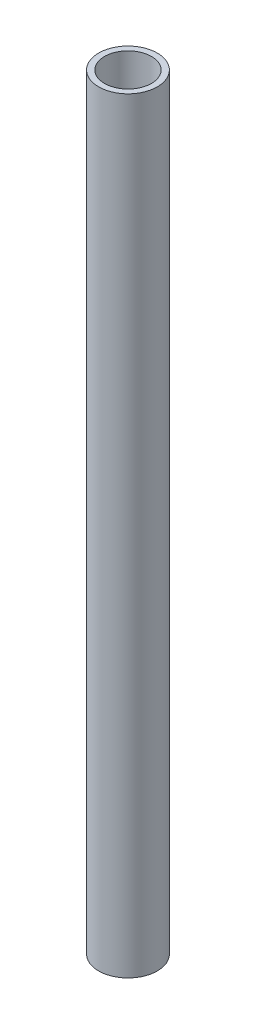
SolidWorks part; units mm, degrees
ref_plane "Front Plane" through (0, 0, 0) normal (0, 0, 1) x (1, 0, 0)
ref_plane "Top Plane" through (0, 0, 0) normal (0, 1, 0) x (1, 0, 0)
ref_plane "Right Plane" through (0, 0, 0) normal (1, 0, 0) x (0, 0, -1)
sketch "Sketch1" plane through (0, 0, 0) normal (0, 1, 0) x (1, 0, 0)
  circle A0 centre (0, 0) radius 17.5
  circle A1 centre (0, 0) radius 14
  dimension "D1" = 35
  dimension "D2" = 28
extrude "Boss-Extrude1" add sketch "Sketch1" along normal mid plane 457.2
